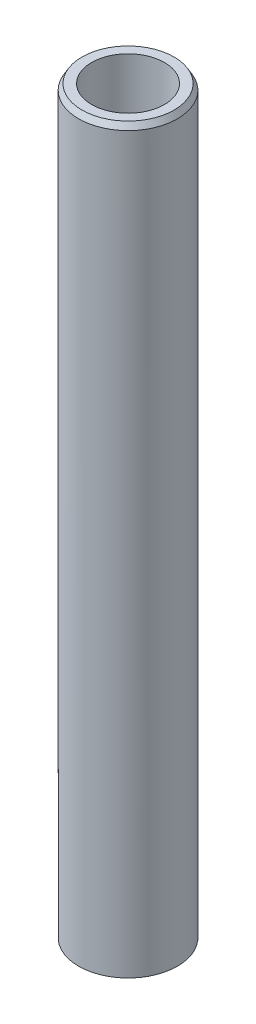
SolidWorks part; units mm, degrees
ref_plane "Front Plane" through (0, 0, 0) normal (0, 0, 1) x (1, 0, 0)
ref_plane "Top Plane" through (0, 0, 0) normal (0, 1, 0) x (1, 0, 0)
ref_plane "Right Plane" through (0, 0, 0) normal (1, 0, 0) x (0, 0, -1)
sketch "Sketch1" plane through (0, 0, 0) normal (0, 1, 0) x (1, 0, 0)
  circle A0 centre (0, 0) radius 25
  dimension "SHAFT_OD" = 50
extrude "Boss-Extrude1" add sketch "Sketch1" along normal blind 375.961
sketch "Sketch2" plane through (0, 0, 0) normal (0, 1, 0) x (1, 0, 0)
  circle A0 centre (0, 0) radius 18.4328
  dimension "BORE_D" = 36.8656
extrude "Cut-Extrude1" cut sketch "Sketch2" along normal through all
chamfer "Chamfer1" distance 2.9738 angle 30 2 edges at (0, 375.961, 25) (0, 0, 25) first distance on face at (0, 375.961, 25) first distance on face at (0, 0, 18.4328)
